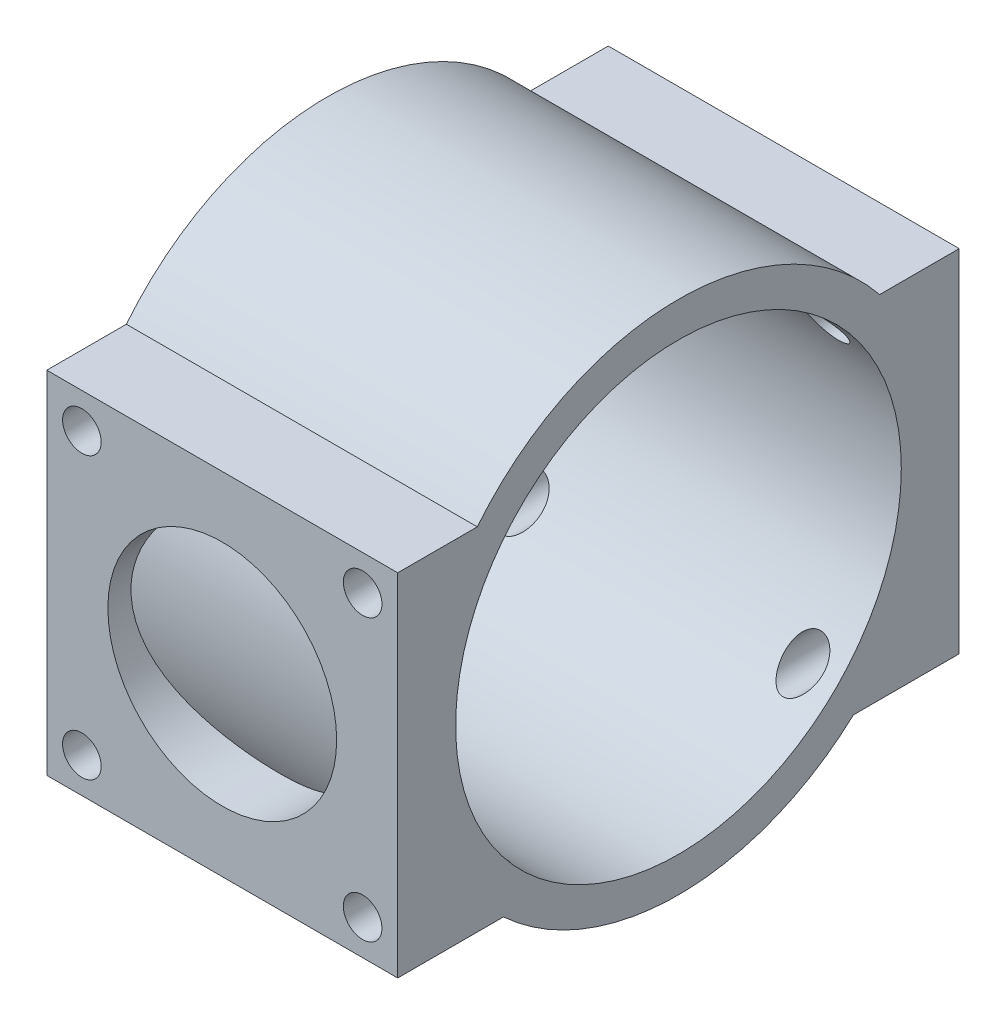
SolidWorks part; units mm, degrees
ref_plane "Front Plane" through (0, 0, 0) normal (0, 0, 1) x (1, 0, 0)
ref_plane "Top Plane" through (0, 0, 0) normal (0, 1, 0) x (1, 0, 0)
ref_plane "Right Plane" through (0, 0, 0) normal (1, 0, 0) x (0, 0, -1)
sketch "Sketch1" plane through (0, 0, 0) normal (0, 0, 1) x (1, 0, 0)
  line L1 (-25, 23) -> (25, 23)
  line L2 (-25, 23) -> (-25, -27)
  line L3 (-25, -27) -> (25, -27)
  line L4 (25, 23) -> (25, -27)
  line L5 (-25, 23) -> (25, -27) construction
  line L6 (-25, -27) -> (25, 23) construction
  circle A0 centre (0, -2) radius 16.3
  circle A1 centre (-20, 18) radius 2.75
  circle A2 centre (20, 18) radius 2.75
  circle A3 centre (20, -22) radius 2.75
  circle A4 centre (-20, -22) radius 2.75
  point P0 (0, -2)
  dimension "D4" = 32.6
  dimension "D6" = 5.5
  dimension "D1" = 2
  dimension "D2" = 50
  dimension "D3" = 50
  dimension "D5" = 20
  dimension "D7" = 20
  dimension "D9" = 20
  dimension "D10" = 20
extrude "Boss-Extrude1" add sketch "Sketch1" along normal blind 40
sketch "Sketch2" plane through (0, 0, 0) normal (1, 0, 0) x (0, 0, -1)
  circle A0 centre (0, 0) radius 31.75
  dimension "D1" = 63.5
extrude "Cut-Extrude1" cut sketch "Sketch2" against normal through all and the other way through all
sketch "Sketch3" plane through (25, 0, 0) normal (1, 0, 0) x (0, 0, -1)
  arc A0 (-21.8875, 23) -> (-16.7052, -27) centre (0, 0) ccw construction
  arc A1 (-21.8875, 23) -> (-16.7052, -27) centre (0, 0) ccw
  arc A2 (-21.8875, 23) -> (-16.7052, -27) centre (0, 0) cw
  arc A3 (-25.3343, 26.622) -> (-19.3359, -31.252) centre (0, 0) cw
  arc A4 (-25.3343, 26.622) -> (-19.3359, -31.252) centre (0, 0) ccw
  arc M2 (-16.7052, -27) -> (-21.8875, 23) centre (0, 0) cw
  dimension "D1" = 5
extrude "Boss-Extrude2" add sketch "Sketch3" against normal blind 50
extrude "Cut-Extrude2" cut sketch "Sketch1<2>" against normal through all and the other way blind 50 contours A1 | A4 | A3 | A2 region at (-20, 18, 0)
sketch "Sketch1<2>" plane through (0, 0, 0) normal (0, 0, 1) x (1, 0, 0) same geometry as "Sketch1"
extrude "Boss-Extrude3" add sketch "Sketch1<3>" against normal blind 40
sketch "Sketch1<3>" plane through (0, 0, 0) normal (0, 0, 1) x (1, 0, 0) same geometry as "Sketch1"
extrude "Cut-Extrude3" cut sketch "Sketch3<2>" against normal through all contours A2 M2 region at (25, 0, 0)
sketch "Sketch3<2>" plane through (25, 0, 0) normal (1, 0, 0) x (0, 0, -1) same geometry as "Sketch3"
scale "Scale1" scale about centroid uniform scaling yes scale factor 1.015
